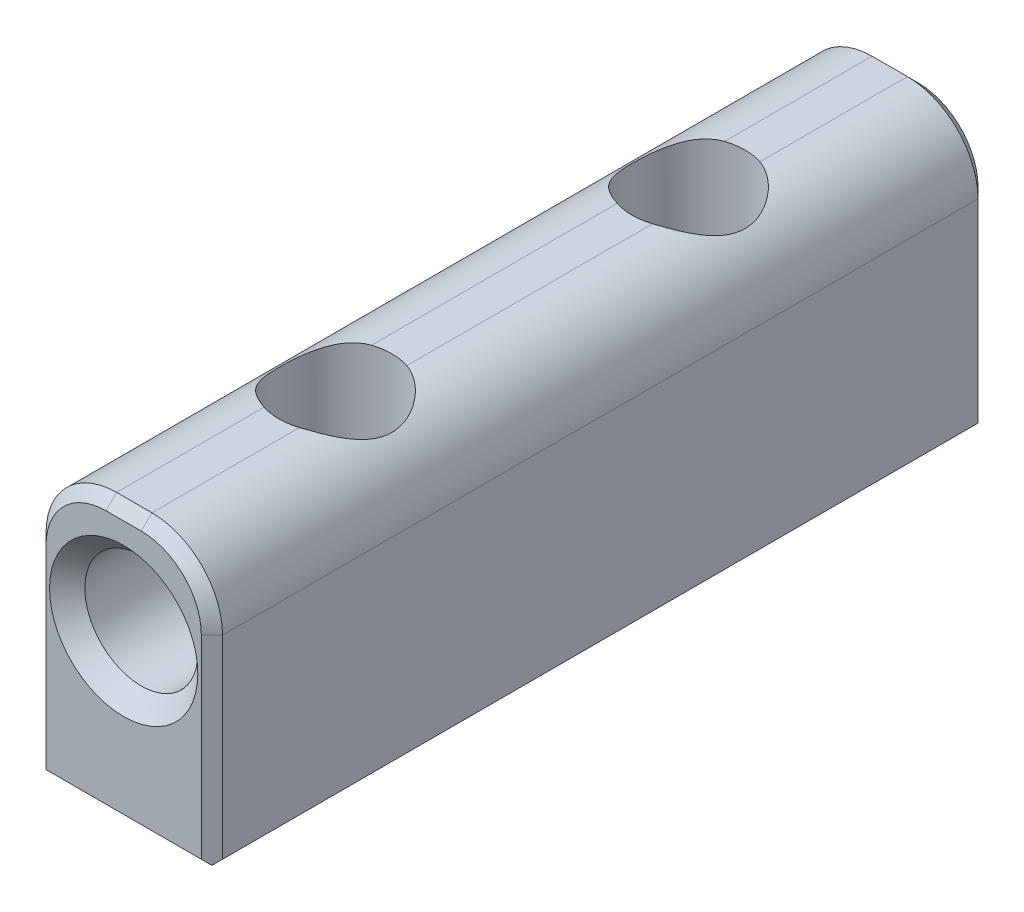
SolidWorks part; units mm, degrees
ref_plane "Front Plane" through (0, 0, 0) normal (0, 0, 1) x (1, 0, 0)
ref_plane "Top Plane" through (0, 0, 0) normal (0, 1, 0) x (1, 0, 0)
ref_plane "Right Plane" through (0, 0, 0) normal (1, 0, 0) x (0, 0, -1)
sketch "Sketch1" plane through (0, 0, 0) normal (0, 1, 0) x (1, 0, 0)
  line L0 (0, -6.35) -> (0, 6.35) construction
  line L1 (3.175, -13.97) -> (-3.175, -13.97)
  line L2 (3.175, -13.97) -> (3.175, 13.97)
  line L3 (3.175, 13.97) -> (-3.175, 13.97)
  line L4 (-3.175, -13.97) -> (-3.175, 13.97)
  line L5 (3.175, -13.97) -> (-3.175, 13.97) construction
  line L6 (3.175, 13.97) -> (-3.175, -13.97) construction
  circle A0 centre (0, 6.35) radius 2.032
  circle A1 centre (0, -6.35) radius 2.032
  point P0 (0, 0)
  point P9 (0, 0)
  dimension "D4" = 4.064
  dimension "D1" = 27.94
  dimension "D2" = 6.35
  dimension "D3" = 12.7
extrude "Boss-Extrude1" add sketch "Sketch1" along normal blind 10.16
sketch "Sketch2" plane through (0, 0, 13.97) normal (0, 0, 1) x (1, 0, 0)
  line L0 (-3.175, 0) -> (3.175, 0) construction
  line L1 (-3.175, 10.16) -> (-3.175, 0) construction
  circle A0 centre (0, 6.35) radius 2.032
  point P6 (-4.1265, 0.4801)
  dimension "D1" = 4.064
  dimension "D2" = 6.35
  dimension "D3" = 3.175
extrude "Cut-Extrude1" cut sketch "Sketch2" against normal blind 3.81
sketch "Sketch4" plane through (0, 0, -13.97) normal (0, 0, -1) x (-1, 0, 0)
  line L0 (-3.175, 0) -> (3.175, 0) construction
  line L1 (-3.175, 10.16) -> (-3.175, 0) construction
  circle A0 centre (0, 6.35) radius 2.032
  point P6 (-4.7812, 2.0739)
  dimension "D1" = 4.064
  dimension "D2" = 6.35
  dimension "D3" = 3.175
extrude "Cut-Extrude2" cut sketch "Sketch4" against normal blind 3.81
fillet "Fillet1" radius 2.54 2 edges at (3.175, 10.16, 0) (-3.175, 10.16, 0)
chamfer "Chamfer1" distance 0.635 angle 45 8 edges at (0, 0, 8.382) (0, 0, -4.318) (0, 0, 13.97) (3.175, 0, 0) (0, 0, -13.97) (-3.175, 0, 0) (-2.032, 6.35, -13.97) (2.032, 6.35, 13.97)
chamfer "Chamfer2" distance 0.381 angle 45 10 edges at (-3.175, 4.1275, -13.97) (-2.4311, 9.4161, -13.97) (0, 10.16, -13.97) (2.4311, 9.4161, -13.97) (3.175, 4.1275, -13.97) (-3.175, 4.1275, 13.97) (-2.4311, 9.4161, 13.97) (0, 10.16, 13.97) (2.4311, 9.4161, 13.97) (3.175, 4.1275, 13.97)
